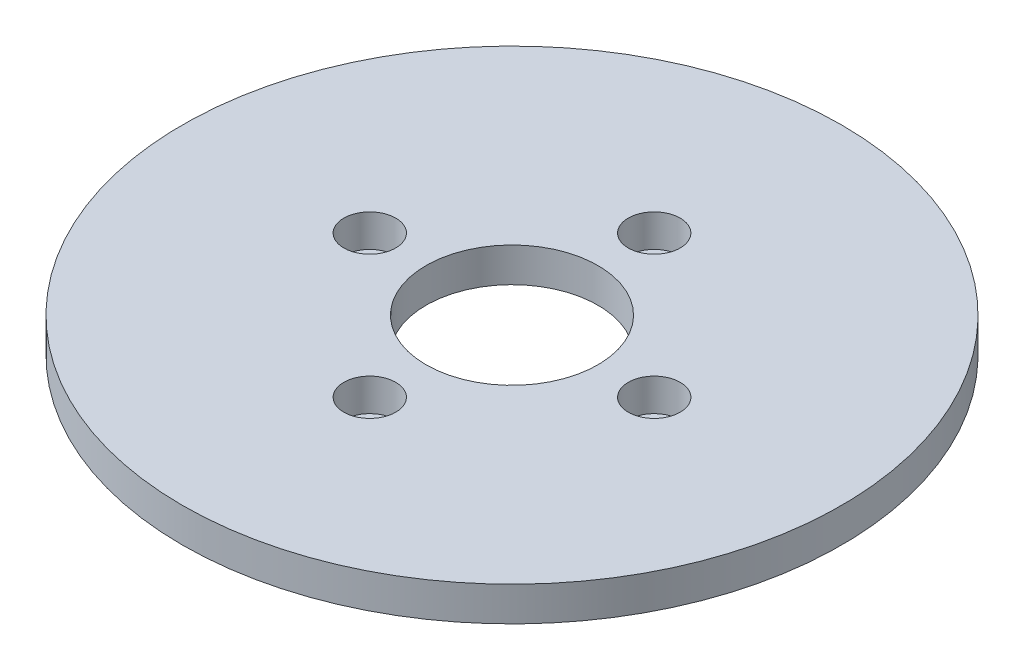
SolidWorks part; units mm, degrees
ref_plane "Front Plane" through (0, 0, 0) normal (0, 0, 1) x (1, 0, 0)
ref_plane "Top Plane" through (0, 0, 0) normal (0, 1, 0) x (1, 0, 0)
ref_plane "Right Plane" through (0, 0, 0) normal (1, 0, 0) x (0, 0, -1)
sketch "Sketch1" plane through (0, 0, 0) normal (0, 1, 0) x (1, 0, 0)
  circle A0 centre (0, 0) radius 57.5
  dimension "FLANGE_OD" = 115
extrude "Boss-Extrude1" add sketch "Sketch1" along normal blind 6
sketch "Sketch2" plane through (0, 0, 0) normal (0, 1, 0) x (1, 0, 0)
  circle A0 centre (0, 0) radius 15
  dimension "BORE_D" = 30
extrude "Cut-Extrude1" cut sketch "Sketch2" along normal through all
sketch "Sketch3" plane through (0, 6, 0) normal (0, 1, 0) x (1, 0, 0)
  circle A0 centre (0, 0) radius 24.8134 construction
  circle A1 centre (-24.8134, 0) radius 4.5263
  dimension "BOLT_D" = 9.0527
  dimension "BOLT_PCD" = 49.6268
extrude "Cut-Extrude2" cut sketch "Sketch3" against normal blind 5.6772
pattern_circular "CirPattern1" count 4 over 360 about axis through (0, 0, 0) along (0, 1, 0) of "Cut-Extrude2"
